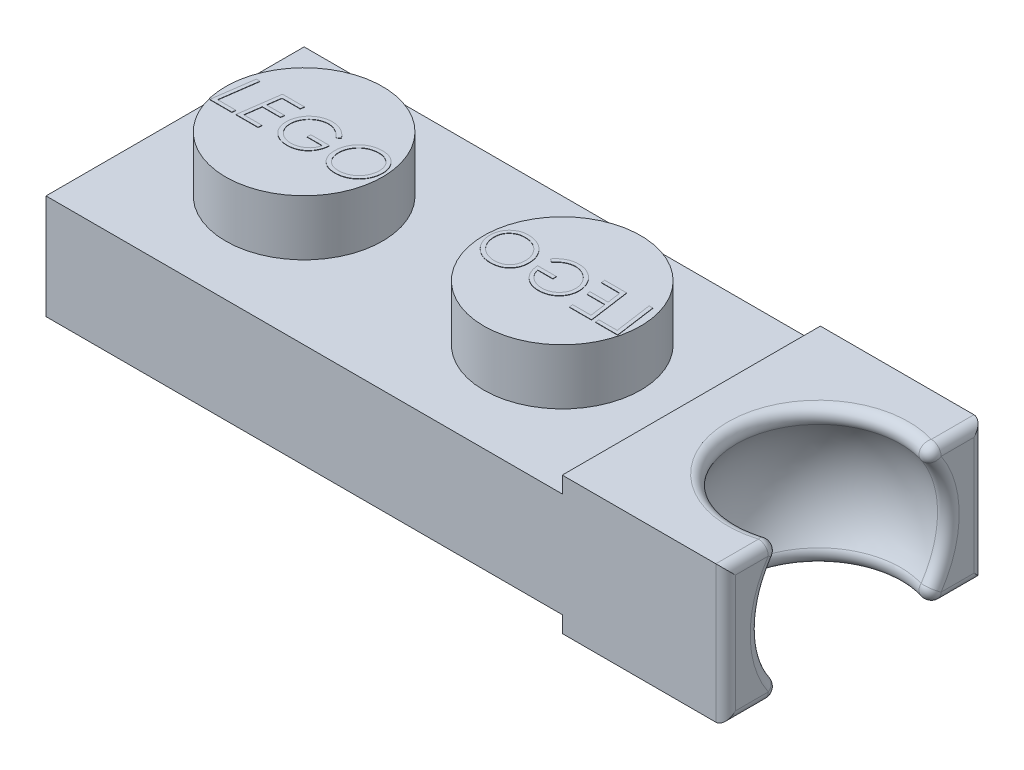
SolidWorks part; units mm, degrees
ref_plane "Front Plane" through (0, 0, 0) normal (0, 0, 1) x (1, 0, 0)
ref_plane "Top Plane" through (0, 0, 0) normal (0, 1, 0) x (1, 0, 0)
ref_plane "Right Plane" through (0, 0, 0) normal (1, 0, 0) x (0, 0, -1)
sketch "Sketch1" plane through (0, 0, 0) normal (0, 1, 0) x (1, 0, 0)
  line L0 (0, 0) -> (7.9, 0)
  line L1 (7.9, 0) -> (7.9, 7.9)
  line L2 (0, 0) -> (0, 7.9)
  line L3 (0, 7.9) -> (7.9, 7.9)
  dimension "D1" = 7.9
  dimension "D2" = 7.9
  dimension "D3" = 7.9
extrude "Boss-Extrude1" add sketch "Sketch1" along normal blind 3.2
sketch "Sketch2" plane through (0, 3.2, 0) normal (0, 1, 0) x (1, 0, 0)
  line L0 (0, 7.9) -> (7.9, 0) construction
  circle A0 centre (3.95, 3.95) radius 2.4
extrude "Boss-Extrude2" add sketch "Sketch2" along normal blind 1.7
sketch "Sketch3" plane through (0, 4.9, 0) normal (0, 1, 0) x (1, 0, 0)
  line L0 (1.625, 3.3549) -> (6.275, 3.3549) construction
  circle A0 centre (3.95, 3.95) radius 2.4 construction
  circle A1 centre (3.95, 3.95) radius 2.4 construction
  text T0 "<i>LEGO</i>" font "Century Gothic" height 1.25
extrude "Boss-Extrude4" add sketch "Sketch3" along normal blind 0.01
sketch "Sketch4" plane through (0, 0, 0) normal (0, -1, 0) x (1, 0, 0)
  line L0 (7.9, -7.9) -> (0, -7.9) construction
  line L1 (7.3, -7.3) -> (0.6204, -7.3)
  line L2 (7.3, -7.3) -> (7.3, -0.6204)
  line L3 (7.3, -0.6204) -> (0.6204, -0.6204)
  line L4 (0.6204, -7.3) -> (0.6204, -0.6204)
  line L5 (7.9, 0) -> (7.9, -7.9) construction
  dimension "D1" = 0.6
  dimension "D2" = 0.6
extrude "Cut-Extrude1" cut sketch "Sketch4" against normal blind 2.01 contours L2 L1 L4 L3
sketch "Sketch5" plane through (0, 3.2, 0) normal (0, 1, 0) x (1, 0, 0)
  line L1 (1.4581, 1.5578) -> (6.3695, 1.5578)
  line L2 (1.4581, 1.5578) -> (1.4581, 6.3652)
  line L3 (1.4581, 6.3652) -> (6.3695, 6.3652)
  line L4 (6.3695, 1.5578) -> (6.3695, 6.3652)
  circle A1 centre (6.3695, 6.3652) radius 1.0161
  circle A2 centre (6.3695, 1.5578) radius 1.0061
  circle A3 centre (1.4581, 1.5578) radius 1.0219
  circle A4 centre (1.4581, 6.3652) radius 1.0411
  circle M5 centre (3.95, 3.95) radius 2.4
extrude "Boss-Extrude5" add sketch "Sketch5" against normal blind 2.01 contours L1 A2 L4 | L2 A3 L1 | L1 A3 L2 | L4 A2 L1 M5 | L4 A1 L3 | L3 A1 L4 | L2 A4 L3 | L3 A4 L2 region at (1.8919, 3.2, -1.9915) region at (1.3136, 3.2, -1.4132) region at (1.3108, 3.2, -6.5125) region at (1.9, 3.2, -5.9234) region at (5.9427, 3.2, -1.9847) region at (6.5119, 3.2, -1.4155) region at (6.5133, 3.2, -6.509) region at (5.9383, 3.2, -5.934)
mirror "Mirror1" about plane through (7.9, 3.2, 0) normal (-1, 0, 0) of bodies 106
sketch "Sketch6" plane through (15.8, 0, 0) normal (1, 0, 0) x (0, 0, -1)
  line L0 (7.9, 3.2) -> (7.9, 0) construction
  line L1 (0, -0.5) -> (7.9, -0.5)
  line L2 (0, -0.5) -> (0, 3.7)
  line L3 (0, 3.7) -> (7.9, 3.7)
  line L4 (7.9, -0.5) -> (7.9, 3.7)
  line L5 (0, 3.2) -> (0, 0) construction
  line L6 (7.9, 0) -> (0, 0) construction
  line L7 (7.9, 3.2) -> (0, 3.2) construction
  dimension "D1" = 0.5
  dimension "D2" = 0.5
extrude "Boss-Extrude6" add sketch "Sketch6" along normal blind 5
ref_plane "Plane1" through (0, 1.6, 0) normal (0, 1, 0) x (1, 0, 0)
sketch "Sketch13" plane through (0, 1.6, 0) normal (0, 1, 0) x (1, 0, 0)
  line L0 (20.8, 3.95) -> (15.8, 3.95) construction
  line L1 (20.8, 7.9) -> (20.8, 0) construction
  line L2 (15.8, 7.9) -> (15.8, 0) construction
  line L3 (19.6889, 0.95) -> (19.6889, 6.95)
  arc A0 (19.6889, 6.95) -> (19.6889, 0.95) centre (19.6889, 3.95) ccw
revolve "Cut-Revolve1" cut sketch "Sketch13" angle 360 about L3
fillet "Fillet1" radius 0.3 10 edges at (20.8, 3.7, -6.8409) (20.8, 1.6, -7.9) (20.8, -0.5, -6.8409) (20.8, -0.5, -1.0591) (20.8, 3.7, -1.0591) (20.8, 1.6, 0) (17.5465, -0.5, -3.95) (20.8, 1.6, -6.7367) (17.5465, 3.7, -3.95) (20.8, 1.6, -1.1633)
